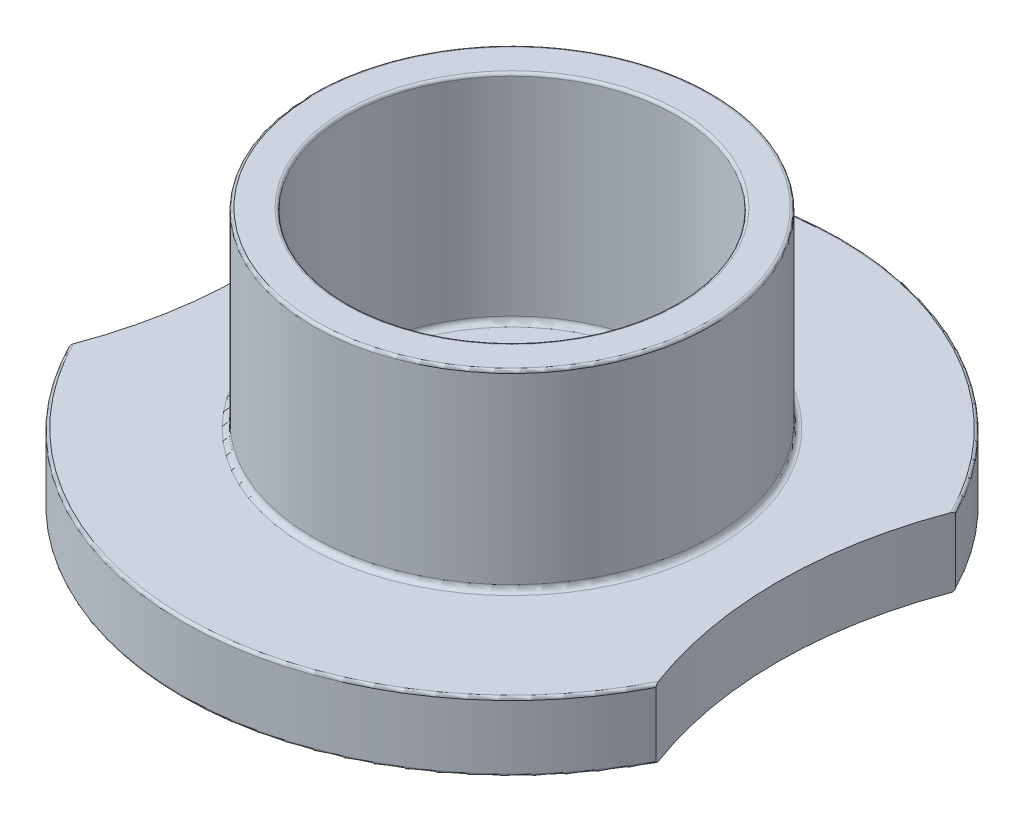
SolidWorks part; units mm, degrees
ref_plane "Plano frontal" through (0, 0, 0) normal (0, 0, 1) x (1, 0, 0)
ref_plane "Plano superior" through (0, 0, 0) normal (0, 1, 0) x (1, 0, 0)
ref_plane "Plano direito" through (0, 0, 0) normal (1, 0, 0) x (0, 0, -1)
sketch "Esboço1" plane through (0, 0, 0) normal (0, 0, 1) x (1, 0, 0)
  line L0 (0, -51.2195) -> (0, 53.1646) construction
  line L1 (29.75, 23.5826) -> (36, 23.5826)
  line L2 (36, 23.5826) -> (36, -10.9174)
  line L3 (36, -10.9174) -> (59.5, -10.9174)
  line L4 (59.5, -10.9174) -> (59.5, -23.4174)
  line L5 (59.5, -23.4174) -> (30.5, -23.4174)
  line L6 (30.5, -23.4174) -> (30.5, -32.4174)
  line L7 (30.5, -32.4174) -> (30, -32.4174)
  line L8 (30, -32.4174) -> (30, -41.4174)
  line L9 (30, -41.4174) -> (23, -41.4174)
  line L10 (23, -41.4174) -> (23, -15.4174)
  line L11 (23, -15.4174) -> (29.75, -15.4174)
  line L12 (29.75, -15.4174) -> (29.75, 23.5826)
  dimension "D1" = 29.75
  dimension "D2" = 36
  dimension "D3" = 23
  dimension "D4" = 30
  dimension "D5" = 30.5
  dimension "D6" = 9
  dimension "D7" = 18
  dimension "D8" = 12.5
  dimension "D9" = 34.5
  dimension "D10" = 39
  dimension "D11" = 59.5
revolve "Revolução1" add sketch "Esboço1" angle 360 about L0
sketch "Esboço2" plane through (0, -23.4174, 0) normal (0, -1, 0) x (1, 0, 0)
  line L0 (0, 0) -> (59.5, 0) construction
  line L1 (0, 0) -> (0, -87.8334) construction
  circle A0 centre (0, 0) radius 59.5 construction
  circle A1 centre (122.9926, 0) radius 75
  circle A2 centre (-122.9926, 0) radius 75
extrude "Corte-extrusão1" cut sketch "Esboço2" against normal through all
fillet "Filete1" radius 0.5 2 edges at (0, 23.5826, -29.75) (0, 23.5826, -36)
fillet "Filete2" radius 1 1 edges at (0, -10.9174, -36)
fillet "Filete3" radius 1 1 edges at (0, -15.4174, -29.75)
chamfer "Chanfro1" distance 1 angle 30 1 edges at (0, -15.4174, -23)
fillet "Filete4" radius 0.5 2 edges at (0, -41.4174, -23) (0, -41.4174, -30)
fillet "Filete5" radius 1 1 edges at (0, -23.4174, -30.5)
fillet "Filete6" radius 0.5 1 edges at (0, -32.4174, -30)
fillet "Filete7" radius 0.5 4 edges at (0, -10.9174, 59.5) (0, -10.9174, -59.5) (0, -23.4174, -59.5) (0, -23.4174, 59.5)
